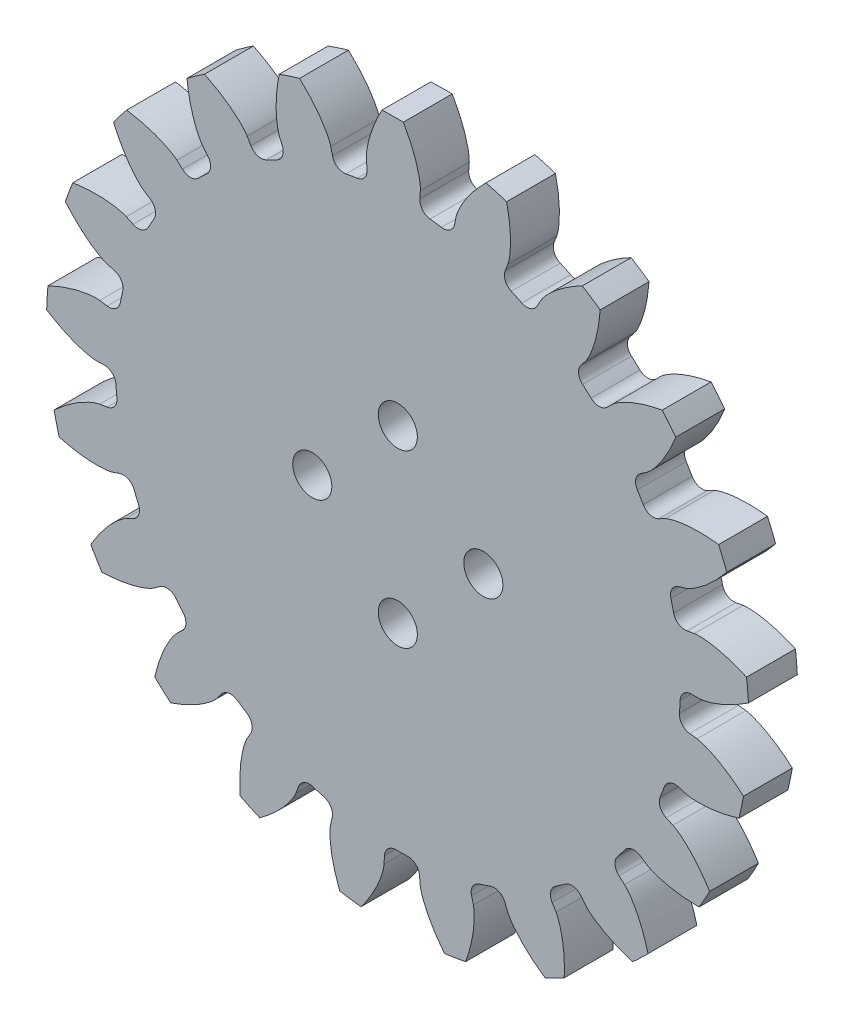
SolidWorks part; units mm, degrees
ref_plane "前基準面" through (0, 0, 0) normal (0, 0, 1) x (1, 0, 0)
ref_plane "上基準面" through (0, 0, 0) normal (0, 1, 0) x (1, 0, 0)
ref_plane "右基準面" through (0, 0, 0) normal (1, 0, 0) x (0, 0, -1)
sketch "草圖1" plane through (0, 0, 0) normal (0, 0, 1) x (1, 0, 0)
  spline S0 degree 4 poles (24.6669, 0) (24.6782, 0.0002) (24.7097, 0.0013) (24.7693, 0.0057) (24.8662, 0.016) (24.9894, 0.034) (25.148, 0.0627) (25.3339, 0.1034) (25.5371, 0.1555) (25.7567, 0.2199) (25.9744, 0.2911) (26.19, 0.3684) (26.4035, 0.4512) (26.6602, 0.5581) (26.9655, 0.6956) (27.3181, 0.8697) (27.7128, 1.0829) (28.109, 1.3166) (28.4936, 1.5601) (28.8757, 1.8213) (29.2408, 2.0848) (29.6128, 2.3737) (29.9525, 2.6482) (30.3246, 2.9722) (30.6224, 3.2385) (31.0057, 3.607) (31.2292, 3.8297) (31.4872, 4.0961) (31.6, 4.2175) (31.6695, 4.2922) knots 0 0 0 0 0 0.005377 0.015084 0.028532 0.04661 0.064855 0.092111 0.119476 0.146842 0.174209 0.201575 0.228941 0.256307 0.307035 0.361767 0.4165 0.471232 0.525964 0.580697 0.635429 0.690161 0.744894 0.799626 0.854358 0.909091 0.954545 1 1 1 1 1 construction
  spline S1 degree 4 poles (24.6669, 0) (24.6782, 0.0002) (24.7097, 0.0013) (24.7693, 0.0057) (24.8662, 0.016) (24.9894, 0.034) (25.148, 0.0627) (25.3339, 0.1034) (25.5371, 0.1555) (25.7567, 0.2199) (25.9744, 0.2911) (26.19, 0.3684) (26.4035, 0.4512) (26.6602, 0.5581) (26.9655, 0.6956) (27.3181, 0.8697) (27.7128, 1.0829) (28.109, 1.3166) (28.4936, 1.5601) (28.8757, 1.8213) (29.2408, 2.0848) (29.6128, 2.3737) (29.9525, 2.6482) (30.3246, 2.9722) (30.6224, 3.2385) (30.9226, 3.5271) (31.0676, 3.6695) (31.1412, 3.7431) knots 0 0 0 0 0 0.005377 0.015084 0.028532 0.04661 0.064855 0.092111 0.119476 0.146842 0.174209 0.201575 0.228941 0.256307 0.307035 0.361767 0.4165 0.471232 0.525964 0.580697 0.635429 0.690161 0.744894 0.799626 0.854358 0.909091 0.909091 0.909091 0.909091 0.909091
sketch "草圖2" plane through (0, 0, 0) normal (0, 0, 1) x (1, 0, 0)
  line L0 (0, 0) -> (34.1478, 0) construction
  line L1 (0, 0) -> (26.2031, -1.5678) construction
  line L2 (24.6669, 0) -> (23.125, 0)
  line L3 (24.4909, -2.9413) -> (22.96, -2.7574)
  circle A0 centre (0, 0) radius 24.665
  circle A1 centre (0, 0) radius 28.75
  circle A2 centre (0, 0) radius 23.125
  arc A3 (26.2031, -1.5678) -> (26.2471, 0.3912) centre (0, 0) ccw
  spline S0 degree 4 poles (-2.4676, 1999.757) (21.3826, 28.5985) (22.5381, 0.4675) (23.7175, -0.1068) (24.8662, 0.016) (24.9894, 0.034) (25.148, 0.0627) (25.3339, 0.1034) (25.5371, 0.1555) (25.7567, 0.2199) (25.9744, 0.2911) (26.19, 0.3684) (26.4035, 0.4512) (26.6602, 0.5581) (26.9655, 0.6956) (27.3181, 0.8697) (27.7128, 1.0829) (28.109, 1.3166) (28.4936, 1.5601) (28.8757, 1.8213) (29.2408, 2.0848) (29.6128, 2.3737) (29.9525, 2.6482) (30.3246, 2.9722) (31.7171, 4.2174) (35.7093, 8.489) (-10.1397, -36.8196) (1444.5525, 1418.6345) knots -0.505535 -0.505535 -0.505535 -0.505535 -0.505535 0.005377 0.015084 0.028532 0.04661 0.064855 0.092111 0.119476 0.146842 0.174209 0.201575 0.228941 0.256307 0.307035 0.361767 0.4165 0.471232 0.525964 0.580697 0.635429 0.690161 0.744894 0.799626 0.854358 1.713796 1.713796 1.713796 1.713796 1.713796 only from (24.6669, 0) to (31.1412, 3.7431) construction
  spline S1 degree 4 poles (24.6669, 0) (24.6782, 0.0002) (24.7097, 0.0013) (24.7693, 0.0057) (24.8662, 0.016) (24.9894, 0.034) (25.148, 0.0627) (25.3339, 0.1034) (25.5371, 0.1555) (25.7567, 0.2199) (25.9744, 0.2911) (26.19, 0.3684) (26.4035, 0.4512) (26.6602, 0.5581) (26.9655, 0.6956) (27.3181, 0.8697) (27.7128, 1.0829) (28.109, 1.3166) (28.4936, 1.5601) (28.8757, 1.8213) (29.2408, 2.0848) (29.6128, 2.3737) (29.9525, 2.6482) (30.3246, 2.9722) (30.6224, 3.2385) (30.9226, 3.5271) (31.0676, 3.6695) (31.1412, 3.7431) knots 0 0 0 0 0 0.005377 0.015084 0.028532 0.04661 0.064855 0.092111 0.119476 0.146842 0.174209 0.201575 0.228941 0.256307 0.307035 0.361767 0.4165 0.471232 0.525964 0.580697 0.635429 0.690161 0.744894 0.799626 0.854358 0.909091 0.909091 0.909091 0.909091 0.909091
  spline S2 degree 4 poles (24.4909, -2.9413) (24.5021, -2.9428) (24.5333, -2.9477) (24.5919, -2.9591) (24.6869, -2.981) (24.8071, -3.0135) (24.9611, -3.0609) (25.1409, -3.1235) (25.3364, -3.1994) (25.5467, -3.2896) (25.7543, -3.3862) (25.9593, -3.4887) (26.1613, -3.5963) (26.4035, -3.7331) (26.6902, -3.906) (27.0195, -4.121) (27.386, -4.3796) (27.7514, -4.6589) (28.1043, -4.9465) (28.4525, -5.2514) (28.7836, -5.5566) (29.1185, -5.8878) (29.4231, -6.2009) (29.7539, -6.5669) (30.0178, -6.8668) (30.2814, -7.1891) (30.4084, -7.3478) (30.4727, -7.4297) knots 0 0 0 0 0 0.005377 0.015084 0.028532 0.04661 0.064855 0.092111 0.119476 0.146842 0.174209 0.201575 0.228941 0.256307 0.307035 0.361767 0.4165 0.471232 0.525964 0.580697 0.635429 0.690161 0.744894 0.799626 0.854358 0.909091 0.909091 0.909091 0.909091 0.909091
  dimension "D1" = 52.5
  dimension "D2" = 57.5
  dimension "D3" = 46.25
  dimension "D4" = 49.33
  dimension "D5" = 1.96
extrude "填料-伸長1" add sketch "草圖2" along normal blind 4 contours A1
sketch "草圖3" plane through (0, 0, 4) normal (0, 0, 1) x (1, 0, 0)
  line L0 (24.4909, -2.9413) -> (22.96, -2.7574) construction
  line L1 (24.6669, 0) -> (23.125, 0) construction
  line L2 (24.4909, -2.9413) -> (22.96, -2.7574)
  line L3 (24.6669, 0) -> (23.125, 0)
  circle A0 centre (0, 0) radius 28.75 construction
  circle A1 centre (0, 0) radius 23.125 construction
  arc A2 (28.2918, -5.1122) -> (28.6996, 1.7022) centre (0, 0) ccw
  arc A3 (22.96, -2.7574) -> (23.125, 0) centre (0, 0) ccw
  spline S0 degree 4 poles (-240.9013, -1985.1954) (17.8199, -30.9442) (22.3216, -3.1517) (23.561, -2.722) (24.6869, -2.981) (24.8071, -3.0135) (24.9611, -3.0609) (25.1409, -3.1235) (25.3364, -3.1994) (25.5467, -3.2896) (25.7543, -3.3862) (25.9593, -3.4887) (26.1613, -3.5963) (26.4035, -3.7331) (26.6902, -3.906) (27.0195, -4.121) (27.386, -4.3796) (27.7514, -4.6589) (28.1043, -4.9465) (28.4525, -5.2514) (28.7836, -5.5566) (29.1185, -5.8878) (29.4231, -6.2009) (29.7539, -6.5669) (30.988, -7.9693) (34.4423, -12.6864) (-5.677, 37.766) (1265.0881, -1580.7619) knots -0.505535 -0.505535 -0.505535 -0.505535 -0.505535 0.005377 0.015084 0.028532 0.04661 0.064855 0.092111 0.119476 0.146842 0.174209 0.201575 0.228941 0.256307 0.307035 0.361767 0.4165 0.471232 0.525964 0.580697 0.635429 0.690161 0.744894 0.799626 0.854358 1.713796 1.713796 1.713796 1.713796 1.713796 only from (24.4909, -2.9413) to (30.4727, -7.4297) construction
  spline S1 degree 4 poles (-2.4676, 1999.757) (21.3826, 28.5985) (22.5381, 0.4675) (23.7175, -0.1068) (24.8662, 0.016) (24.9894, 0.034) (25.148, 0.0627) (25.3339, 0.1034) (25.5371, 0.1555) (25.7567, 0.2199) (25.9744, 0.2911) (26.19, 0.3684) (26.4035, 0.4512) (26.6602, 0.5581) (26.9655, 0.6956) (27.3181, 0.8697) (27.7128, 1.0829) (28.109, 1.3166) (28.4936, 1.5601) (28.8757, 1.8213) (29.2408, 2.0848) (29.6128, 2.3737) (29.9525, 2.6482) (30.3246, 2.9722) (31.7171, 4.2174) (35.7093, 8.489) (-10.1397, -36.8196) (1444.5525, 1418.6345) knots -0.505535 -0.505535 -0.505535 -0.505535 -0.505535 0.005377 0.015084 0.028532 0.04661 0.064855 0.092111 0.119476 0.146842 0.174209 0.201575 0.228941 0.256307 0.307035 0.361767 0.4165 0.471232 0.525964 0.580697 0.635429 0.690161 0.744894 0.799626 0.854358 1.713796 1.713796 1.713796 1.713796 1.713796 only from (24.6669, 0) to (31.1412, 3.7431) construction
  spline S2 degree 4 poles (24.4909, -2.9413) (24.5021, -2.9428) (24.5333, -2.9477) (24.5919, -2.9591) (24.6869, -2.981) (24.8071, -3.0135) (24.9611, -3.0609) (25.1409, -3.1235) (25.3364, -3.1994) (25.5467, -3.2896) (25.7543, -3.3862) (25.9593, -3.4887) (26.1613, -3.5963) (26.4035, -3.7331) (26.6902, -3.906) (27.0195, -4.121) (27.386, -4.3796) (27.7514, -4.6589) (28.0197, -4.8776) (28.1982, -5.0304) (28.2882, -5.1091) (28.2918, -5.1122) knots 0 0 0 0 0 0.005377 0.015084 0.028532 0.04661 0.064855 0.092111 0.119476 0.146842 0.174209 0.201575 0.228941 0.256307 0.307035 0.361767 0.4165 0.471232 0.525964 0.528234 0.528234 0.528234 0.528234 0.528234
  spline S3 degree 4 poles (24.6669, 0) (24.6782, 0.0002) (24.7097, 0.0013) (24.7693, 0.0057) (24.8662, 0.016) (24.9894, 0.034) (25.148, 0.0627) (25.3339, 0.1034) (25.5371, 0.1555) (25.7567, 0.2199) (25.9744, 0.2911) (26.19, 0.3684) (26.4035, 0.4512) (26.6602, 0.5581) (26.9655, 0.6956) (27.3181, 0.8697) (27.7128, 1.0829) (28.109, 1.3166) (28.4014, 1.5017) (28.5968, 1.6321) (28.6956, 1.6996) (28.6996, 1.7022) knots 0 0 0 0 0 0.005377 0.015084 0.028532 0.04661 0.064855 0.092111 0.119476 0.146842 0.174209 0.201575 0.228941 0.256307 0.307035 0.361767 0.4165 0.471232 0.525964 0.528234 0.528234 0.528234 0.528234 0.528234
extrude "除料-伸長1" cut sketch "草圖3" against normal blind 4
fillet "圓角1" radius 0.95 2 edges at (22.96, -2.7574, 2) (23.125, 0, 2)
pattern_circular "環狀複製排列1" count 21 every 17.14 about axis through (0, 0, 4) along (0, 0, -1) of "圓角1", "除料-伸長1" reverse direction yes
sketch "草圖4" plane through (0, 0, 4) normal (0, 0, 1) x (1, 0, 0)
  line L0 (0, 0) -> (41.7902, 0) construction
  circle A0 centre (7, 0) radius 1.6
  dimension "D1" = 3.2
  dimension "D2" = 7
extrude "除料-伸長2" cut sketch "草圖4" against normal blind 4
pattern_circular "環狀複製排列2" count 4 every 90 about axis through (0, 0, 0) along (0, 0, 1) of "除料-伸長2" reverse direction yes
sketch "草圖5" plane through (0, 0, 4) normal (0, 0, 1) x (1, 0, 0)
  circle A0 centre (0, 0) radius 26.25 construction
  dimension "D1" = 52.5
equation "\"a\"= 20"
equation "\"M\"= 2.5"
equation "\"T\"= 21"
equation "\"R\"= 0.38 * \"M\""
equation "\"D\"= \"M\" * \"T\""
equation "\"Da\"= ( \"T\" + 2 ) * \"M\""
equation "\"Df\"= ( \"T\" - 2.5 ) * \"M\""
equation "\"Db\"= \"M\" * \"T\" * cos ( \"a\" )"
equation "\"rb\"= \"Db\" / 2"
equation "\"S\"= pi * \"M\" * 0.5"
